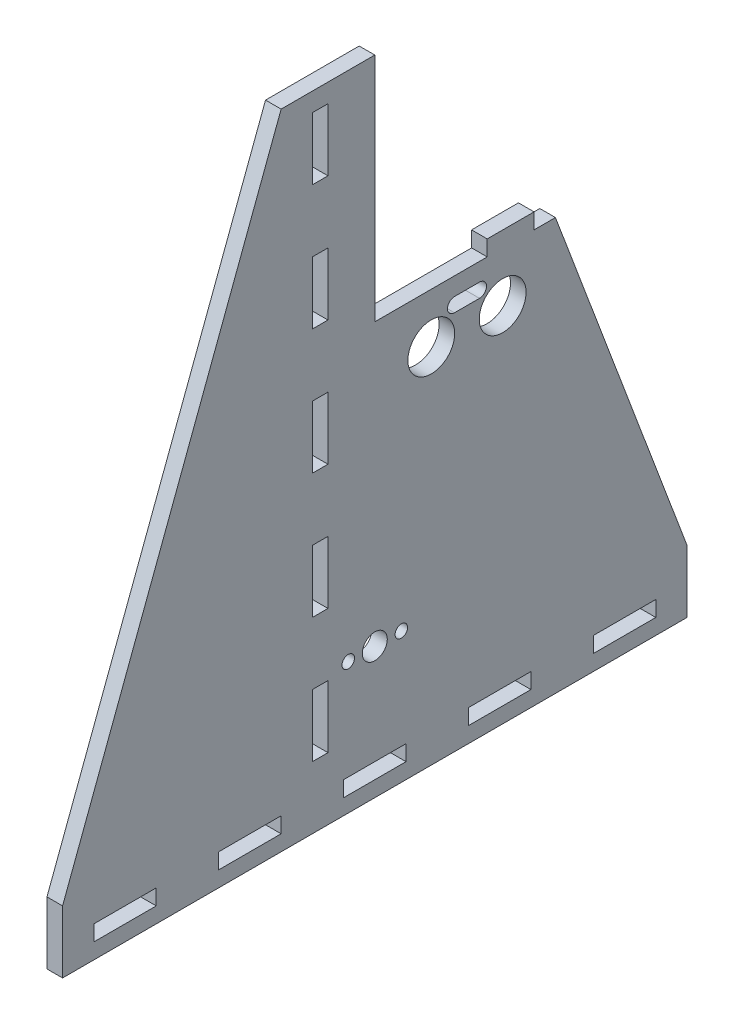
SolidWorks part; units mm, degrees
ref_plane "Přední rovina" through (0, 0, 0) normal (0, 0, 1) x (1, 0, 0)
ref_plane "Horní rovina" through (0, 0, 0) normal (0, 1, 0) x (1, 0, 0)
ref_plane "Pravá rovina" through (0, 0, 0) normal (1, 0, 0) x (0, 0, -1)
sketch "Skica1" plane through (0, 0, 0) normal (1, 0, 0) x (0, 0, -1)
  line L0 (0, 0) -> (0, 200)
  line L1 (-100, 0) -> (100, 0)
  line L2 (-100, 0) -> (-100, 206)
  line L3 (-100, 206) -> (100, 206)
  line L4 (100, 0) -> (100, 206)
  line L5 (-90, 5) -> (-70, 5)
  line L6 (-90, 5) -> (-90, 10)
  line L7 (-90, 10) -> (-70, 10)
  line L8 (-70, 5) -> (-70, 10)
  line L9 (-50, 5) -> (-30, 5)
  line L10 (-50, 5) -> (-50, 10)
  line L11 (-50, 10) -> (-30, 10)
  line L12 (-30, 5) -> (-30, 10)
  line L13 (-10, 5) -> (10, 5)
  line L14 (-10, 5) -> (-10, 10)
  line L15 (-10, 10) -> (10, 10)
  line L16 (10, 5) -> (10, 10)
  line L17 (50, 10) -> (30, 10)
  line L18 (30, 5) -> (30, 10)
  line L19 (50, 5) -> (30, 5)
  line L20 (50, 5) -> (50, 10)
  line L21 (90, 10) -> (70, 10)
  line L22 (70, 5) -> (70, 10)
  line L23 (90, 5) -> (70, 5)
  line L24 (90, 5) -> (90, 10)
  line L25 (-8.5, 42) -> (0, 42)
  line L26 (0, 200) -> (0, 206)
  line L27 (-15, 20) -> (-20, 20)
  line L28 (-15, 20) -> (-15, 40)
  line L29 (-15, 40) -> (-20, 40)
  line L30 (-20, 20) -> (-20, 40)
  line L31 (-15, 60) -> (-20, 60)
  line L32 (-15, 60) -> (-15, 80)
  line L33 (-15, 80) -> (-20, 80)
  line L34 (-20, 60) -> (-20, 80)
  line L35 (-15, 100) -> (-20, 100)
  line L36 (-15, 100) -> (-15, 120)
  line L37 (-15, 120) -> (-20, 120)
  line L38 (-20, 100) -> (-20, 120)
  line L39 (-15, 140) -> (-20, 140)
  line L40 (-15, 140) -> (-15, 160)
  line L41 (-15, 160) -> (-20, 160)
  line L42 (-20, 140) -> (-20, 160)
  line L43 (-15, 180) -> (-20, 180)
  line L44 (-15, 180) -> (-15, 200)
  line L45 (-15, 200) -> (-20, 200)
  line L46 (-20, 180) -> (-20, 200)
  line L47 (-30, 206) -> (-100, 20)
  line L48 (100, 20) -> (30, 206)
  line L49 (57.8495, 132) -> (0, 132)
  line L50 (25.5223, 124) -> (33.5223, 124) construction
  line L51 (36, 132) -> (51, 132)
  line L52 (36, 132) -> (36, 137)
  line L53 (36, 137) -> (51, 137)
  line L54 (51, 132) -> (51, 137)
  line L55 (25.5223, 126.25) -> (33.5223, 126.25)
  line L56 (25.5223, 121.75) -> (33.5223, 121.75)
  circle A0 centre (0, 42) radius 4
  circle A1 centre (-8.5, 42) radius 2
  circle A2 centre (8.5, 42) radius 2
  circle A3 centre (18.0923, 116) radius 7.5
  circle A4 centre (40.9523, 116) radius 7.5
  arc A5 (25.5223, 126.25) -> (25.5223, 121.75) centre (25.5223, 124) ccw
  arc A6 (33.5223, 121.75) -> (33.5223, 126.25) centre (33.5223, 124) ccw
  point P19 (-30, 7.5)
  point P20 (-70, 7.5)
  point P21 (-80, 10)
  point P56 (-17.5, 180)
  point P57 (-30, 206)
  point P59 (30, 206)
  point P76 (29.5223, 124)
  dimension "D13" = 8
  dimension "D15" = 4
  dimension "D31" = 15
  dimension "D33" = 8
  dimension "D37" = 8
  dimension "D1" = 200
  dimension "D2" = 100
  dimension "D3" = 206
  dimension "D4" = 20
  dimension "D5" = 10
  dimension "D6" = 20
  dimension "D7" = 20
  dimension "D8" = 20
  dimension "D9" = 20
  dimension "D10" = 5
  dimension "D11" = 5
  dimension "D12" = 0
  dimension "D14" = 8.5
  dimension "D16" = 37
  dimension "D17" = 10
  dimension "D18" = 20
  dimension "D19" = 20
  dimension "D20" = 20
  dimension "D21" = 20
  dimension "D22" = 20
  dimension "D23" = 20
  dimension "D24" = 20
  dimension "D25" = 20
  dimension "D26" = 20
  dimension "D27" = 5
  dimension "D28" = 15
  dimension "D29" = 30
  dimension "D30" = 22.86
  dimension "D32" = 74
  dimension "D34" = 36
  dimension "D35" = 15
  dimension "D36" = 72.8495
  dimension "D38" = 11.43
  dimension "D39" = 8
  dimension "D40" = 4.5
  dimension "D41" = 5
extrude "Přidat vysunutím1" add sketch "Skica1" along normal blind 5 contours L14 L15 L0 L3 L2 L1 L13 L12 L9 L10 L11 L8 L5 L6 L7 | L16 L13 L0 L1 L4 L3 L15 L24 L23 L22 L21 L20 L19 L18 L17 | L53 L54 L51 L52 region at (0, 84.6396, 38.3205) region at (0, 58.8234, -42.6506)
